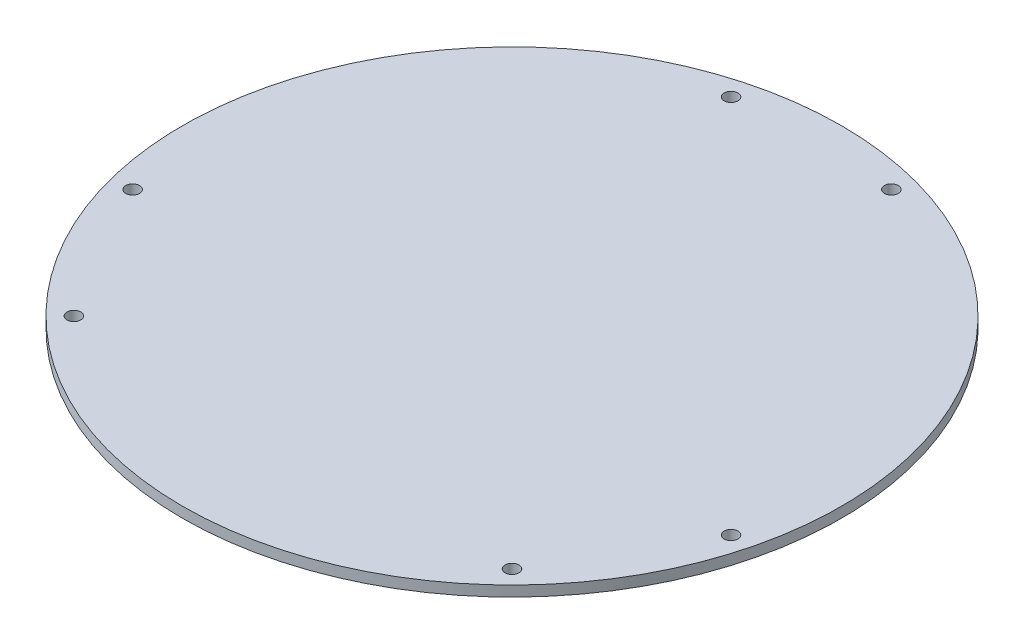
SolidWorks part; units mm, degrees
ref_plane "Front Plane" through (0, 0, 0) normal (0, 0, 1) x (1, 0, 0)
ref_plane "Top Plane" through (0, 0, 0) normal (0, 1, 0) x (1, 0, 0)
ref_plane "Right Plane" through (0, 0, 0) normal (1, 0, 0) x (0, 0, -1)
sketch "Sketch1" plane through (0, 0, 0) normal (0, 1, 0) x (1, 0, 0)
  line L0 (0, 100) -> (0, 0) construction
  line L1 (0, 0) -> (25.8819, 96.5926) construction
  circle A0 centre (0, 0) radius 100
  circle A1 centre (24.329, 90.797) radius 2.1
  circle A2 centre (-24.329, 90.797) radius 2.1
  circle A3 centre (90.797, -24.329) radius 2.1
  circle A4 centre (66.468, -66.468) radius 2.1
  circle A5 centre (-66.468, -66.468) radius 2.1
  circle A6 centre (-90.797, -24.329) radius 2.1
  point P20 (0, 0)
  dimension "D1" = 200
  dimension "D3" = 4.2
  dimension "D2" = 15
  dimension "D4" = 6
extrude "Boss-Extrude1" add sketch "Sketch1" along normal blind 3.175
